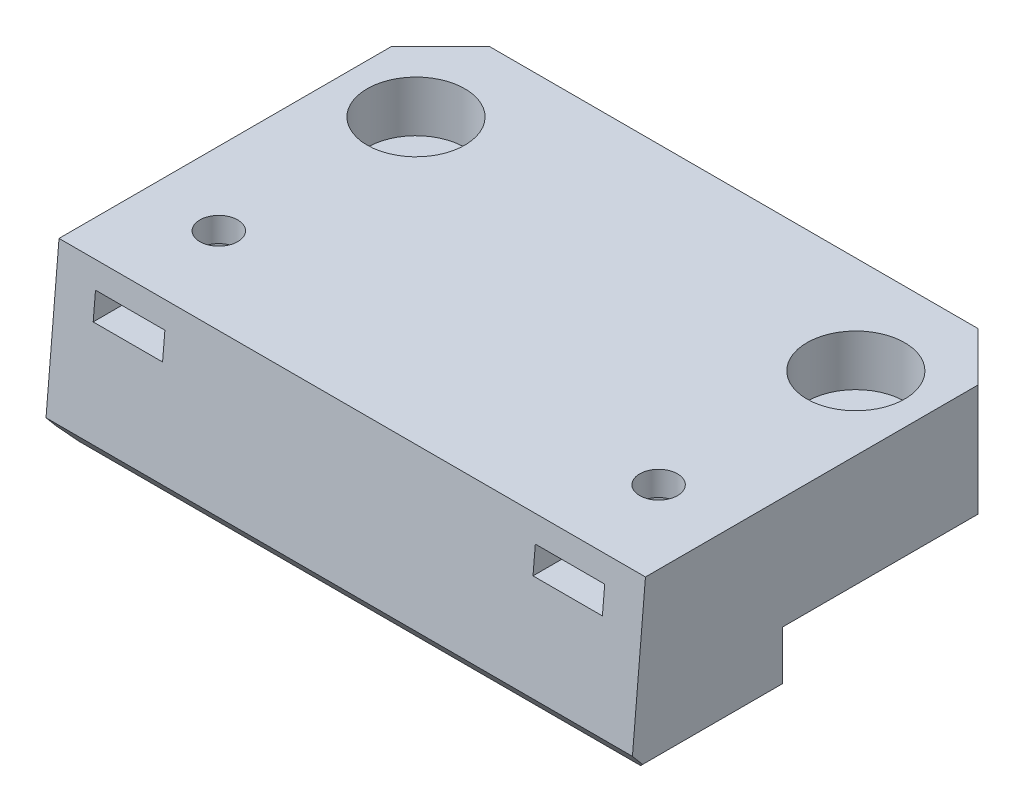
SolidWorks part; units mm, degrees
material "PET"
ref_plane "Front Plane" through (0, 0, 0) normal (0, 0, 1) x (1, 0, 0)
ref_plane "Top Plane" through (0, 0, 0) normal (0, 1, 0) x (1, 0, 0)
ref_plane "Right Plane" through (0, 0, 0) normal (1, 0, 0) x (0, 0, -1)
sketch "Sketch1" plane through (0, 0, 0) normal (1, 0, 0) x (0, 0, -1)
  line L1 (12.7, -4.7625) -> (-12.7, -4.7625)
  line L2 (12.7, -4.7625) -> (12.7, 4.7625)
  line L3 (12.7, 4.7625) -> (-12.7, 4.7625)
  line L4 (-12.7, -4.7625) -> (-12.7, 4.7625)
  line L5 (12.7, -4.7625) -> (-12.7, 4.7625) construction
  line L6 (12.7, 4.7625) -> (-12.7, -4.7625) construction
  point P0 (0, 0)
  dimension "D1" = 9.525
  dimension "D2" = 25.4
extrude "Boss-Extrude1" add sketch "Sketch1" along normal mid plane 76.2
sketch "Sketch2" plane through (-38.1, 0, 0) normal (-1, 0, 0) x (0, 0, 1)
  line L0 (12.7, 4.7625) -> (37.438, 4.7625)
  line L1 (12.7, 4.7625) -> (12.7, -4.7625) construction
  line L2 (37.438, 4.7625) -> (38.829, -11.1363)
  line L4 (38.829, -11.1363) -> (12.7, -11.1363)
  line L9 (12.7, -11.1363) -> (12.7, 4.7625)
  line L10 (-12.7, 4.7625) -> (12.7, 4.7625) construction
  line L11 (25.5674, 149.1875) -> (39.494, -9.9944) construction
  line L12 (19.05, -11.1363) -> (38.1, -11.1363) construction
  dimension "D1" = 0.762
extrude "Boss-Extrude2" add sketch "Sketch2" against normal through all
chamfer "Chamfer1" distance 6.35 angle 45 4 edges at (38.1, -7.9494, 12.7) (38.1, 0, -12.7) (-38.1, 0, -12.7) (-38.1, -7.9494, 12.7)
chamfer "Chamfer2" distance 3.175 angle 45 1 edges at (0, -11.1363, 38.829) first distance on face at (0, -3.1869, 38.1335)
hole_wizard "#8 Clearance Hole1" positions "Sketch3" profile "Sketch4" hole size "#8" standard "ANSI Inch" end condition up to next
sketch "Sketch3" plane through (0, -11.1363, 0) normal (0, -1, 0) x (-1, 0, 0)
  line L0 (0, -38.5523) -> (0, -12.7) construction
  line L1 (38.1, -38.5523) -> (-38.1, -38.5523) construction
  line L2 (-31.75, -12.7) -> (31.75, -12.7) construction
  line L3 (0, -12.7) -> (0, 12.7) construction
  line L4 (-31.75, 12.7) -> (31.75, 12.7) construction
  line L6 (0, 0) -> (38.1, 0) construction
  line L7 (38.1, -19.05) -> (38.1, 6.35) construction
  line L9 (0, -25.6261) -> (38.1, -25.6261) construction
  line L10 (38.1, -19.05) -> (38.1, -35.8983) construction
  point P24 (28.575, -25.6261)
  point P26 (28.575, 0)
  point P35 (-28.575, 0)
  point P36 (-28.575, -25.6261)
  point P38 (0, 0)
  point P39 (0, 0)
  dimension "D1" = 9.525
sketch "Sketch4" plane through (28.575, -11.1363, 25.6261) normal (1, 0, 0) x (0, 0, -1)
  line L0 (0, 0) -> (0, 15.8988)
  line L1 (0, 15.8988) -> (2.4574, 15.8988)
  line L2 (2.4574, 15.8988) -> (2.4574, 0)
  line L5 (2.4574, 0) -> (0, 0)
  line L11 (0, -6.35) -> (0, 107.95) construction
  dimension "Thru Hole Dia." = 4.9149
  dimension "Thru Hole Depth" = 15.8988
chamfer "Chamfer3" distance 1.5875 angle 45 10 edges at (-38.1, -4.7625, 6.35) (-34.925, -4.7625, -9.525) (0, -4.7625, -12.7) (34.925, -4.7625, -9.525) (38.1, -4.7625, 6.35) (38.1, -11.1363, 27.4741) (34.925, -11.1363, 15.875) (0, -11.1363, 12.7) (-34.925, -11.1363, 15.875) (-38.1, -11.1363, 27.4741)
sketch "Sketch5" plane through (0, 4.7625, 0) normal (0, 1, 0) x (1, 0, 0)
  line L0 (38.1, 6.35) -> (38.1, -37.438) construction
  line L1 (33.0835, -37.438) -> (33.0835, -23.0232)
  line L2 (33.0835, -23.0232) -> (28.575, -20.4202)
  line L3 (28.575, -20.4202) -> (24.0665, -23.0232)
  line L4 (24.0665, -23.0232) -> (24.0665, -37.438)
  line L20 (20.8915, -37.438) -> (24.0665, -37.438)
  line L21 (20.8915, -37.438) -> (20.8915, -17.2452)
  line L22 (20.8915, -17.2452) -> (36.2585, -17.2452)
  line L23 (36.2585, -37.438) -> (36.2585, -17.2452)
  line L24 (24.0665, -28.2291) -> (28.575, -30.8321) [skipped]
  line L25 (28.575, -30.8321) -> (33.0835, -28.2291) [skipped]
  line L26 (33.0835, -37.438) -> (36.2585, -37.438)
  line L27 (28.575, -20.4202) -> (28.575, -17.2452) construction
  line L28 (4.5085, -37.438) -> (4.5085, -23.0232) construction
  line L29 (4.5085, -23.0232) -> (0, -20.4202) construction
  line L30 (0, -20.4202) -> (-4.5085, -23.0232) construction
  line L31 (-4.5085, -23.0232) -> (-4.5085, -37.438) construction
  line L32 (-7.6835, -37.438) -> (-4.5085, -37.438) construction
  line L33 (-7.6835, -37.438) -> (-7.6835, -17.2452) construction
  line L34 (-7.6835, -17.2452) -> (7.6835, -17.2452) construction
  line L35 (7.6835, -37.438) -> (7.6835, -17.2452) construction
  line L36 (4.5085, -37.438) -> (7.6835, -37.438) construction
  line L37 (0, -20.4202) -> (0, -17.2452) construction
  line L38 (-24.0665, -37.438) -> (-24.0665, -23.0232)
  line L39 (-24.0665, -23.0232) -> (-28.575, -20.4202)
  line L40 (-28.575, -20.4202) -> (-33.0835, -23.0232)
  line L41 (-33.0835, -23.0232) -> (-33.0835, -37.438)
  line L42 (-36.2585, -37.438) -> (-33.0835, -37.438)
  line L43 (-36.2585, -37.438) -> (-36.2585, -17.2452)
  line L44 (-36.2585, -17.2452) -> (-20.8915, -17.2452)
  line L45 (-20.8915, -37.438) -> (-20.8915, -17.2452)
  line L46 (-24.0665, -37.438) -> (-20.8915, -37.438)
  line L47 (-28.575, -20.4202) -> (-28.575, -17.2452) construction
  line L48 (85.7885, -37.438) -> (4.5085, -37.438) construction
  line L49 (38.1, -37.438) -> (-38.1, -37.438) construction
  circle A0 centre (28.575, -25.6261) radius 4.5085 construction
  circle A1 centre (0, -25.6261) radius 4.5085 construction
  circle A2 centre (-28.575, -25.6261) radius 4.5085 construction
  point P7 (0, 0)
  point P48 (2.8493, -25.6261)
  point P49 (-28.575, -25.6261)
  dimension "D1" = 9.017
  dimension "D2" = 3.175
  dimension "D3" = 3
  dimension "D5" = 0
extrude "Boss-Extrude3" add sketch "Sketch5" along normal blind 3.429
sketch "Sketch6" plane through (0, 8.1915, 0) normal (0, 1, 0) x (1, 0, 0)
  line L0 (20.8915, -37.438) -> (-20.8915, -37.438) construction
  line L1 (-36.2585, -17.2452) -> (-20.8915, -17.2452)
  line L2 (-36.2585, -17.2452) -> (-36.2585, -37.438)
  line L3 (-36.2585, -37.438) -> (-20.8915, -37.438)
  line L4 (-20.8915, -17.2452) -> (-20.8915, -37.438)
  line L5 (-7.6835, -17.2452) -> (7.6835, -17.2452) construction
  line L6 (-7.6835, -17.2452) -> (-7.6835, -37.438) construction
  line L7 (-7.6835, -37.438) -> (7.6835, -37.438) construction
  line L8 (7.6835, -17.2452) -> (7.6835, -37.438) construction
  line L9 (20.8915, -17.2452) -> (36.2585, -17.2452)
  line L10 (20.8915, -17.2452) -> (20.8915, -37.438)
  line L11 (20.8915, -37.438) -> (36.2585, -37.438)
  line L12 (36.2585, -17.2452) -> (36.2585, -37.438)
  line L13 (36.2585, -25.6261) -> (20.8915, -25.6261) construction
  line L14 (0, -37.438) -> (0, -17.2452) construction
  line L15 (-28.575, -37.438) -> (-28.575, -17.2452) construction
  circle A0 centre (28.575, -25.6261) radius 2.4574 construction
  circle A2 centre (-28.575, -25.6261) radius 2.4574 construction
  circle A3 centre (28.575, -25.6261) radius 2.4574
  circle A4 centre (0, -25.6261) radius 2.4574 construction
  circle A5 centre (-28.575, -25.6261) radius 2.4574
  point P32 (28.575, -25.6261)
  point P36 (0, 0)
extrude "Boss-Extrude4" add sketch "Sketch6" along normal blind 3.175
chamfer "Chamfer4" [suppressed] distance 6.604 angle 45
sketch "Sketch7" plane through (0, 4.7625, 0) normal (0, 1, 0) x (1, 0, 0)
  line L42 (-20.8915, -17.2452) -> (-20.8915, -37.438)
  line L44 (-20.8915, -37.438) -> (20.8915, -37.438)
  line L45 (-20.8915, -37.438) -> (20.8915, -37.438)
  line L47 (-20.8915, -17.2452) -> (-20.8915, -37.438)
  line L56 (38.1, -37.438) -> (38.1, 6.35)
  line L57 (38.1, 6.35) -> (31.75, 12.7)
  line L58 (31.75, 12.7) -> (-31.75, 12.7)
  line L59 (-31.75, 12.7) -> (-38.1, 6.35)
  line L60 (-38.1, 6.35) -> (-38.1, -37.438)
  line L74 (38.1, -37.438) -> (38.1, 6.35)
  line L75 (38.1, 6.35) -> (31.75, 12.7)
  line L76 (31.75, 12.7) -> (-31.75, 12.7)
  line L77 (-31.75, 12.7) -> (-38.1, 6.35)
  line L78 (-38.1, 6.35) -> (-38.1, -37.438)
  line L82 (20.8915, -37.438) -> (20.8915, -17.2452)
  line L84 (20.8915, -37.438) -> (20.8915, -17.2452)
  line L86 (20.8915, -17.2452) -> (36.2585, -17.2452)
  line L87 (20.8915, -17.2452) -> (36.2585, -17.2452)
  line L88 (36.2585, -17.2452) -> (36.2585, -37.438)
  line L89 (36.2585, -17.2452) -> (36.2585, -37.438)
  line L90 (36.2585, -37.438) -> (38.1, -37.438)
  line L91 (36.2585, -37.438) -> (38.1, -37.438)
  line L92 (-38.1, -37.438) -> (-36.2585, -37.438)
  line L93 (-38.1, -37.438) -> (-36.2585, -37.438)
  line L94 (-36.2585, -37.438) -> (-36.2585, -17.2452)
  line L95 (-36.2585, -37.438) -> (-36.2585, -17.2452)
  line L96 (-36.2585, -17.2452) -> (-20.8915, -17.2452)
  line L97 (-36.2585, -17.2452) -> (-20.8915, -17.2452)
  circle A0 centre (28.575, 0) radius 6.35
  circle A1 centre (0, 0) radius 6.35 construction
  circle A2 centre (-28.575, 0) radius 6.35
  point P1 (0, 0)
  dimension "D5" = 12.7
  dimension "D1" = 0
extrude "Boss-Extrude5" add sketch "Sketch7" along normal up to surface (6.604 mm away) up to face at (28.575, 11.3665, 27.3416)
sketch "Sketch8" plane through (-38.1, 0, 0) normal (-1, 0, 0) x (0, 0, 1)
  line L0 (37.438, 4.7625) -> (36.8603, 11.3665)
  line L2 (36.8603, 11.3665) -> (37.438, 11.3665)
  line L3 (37.438, 11.3665) -> (37.438, 4.7625)
  line L4 (38.5523, -7.9734) -> (37.438, 4.7625) construction
  line L5 (-6.35, 11.3665) -> (37.438, 11.3665) construction
extrude "Cut-Extrude1" cut sketch "Sketch8" against normal through all
